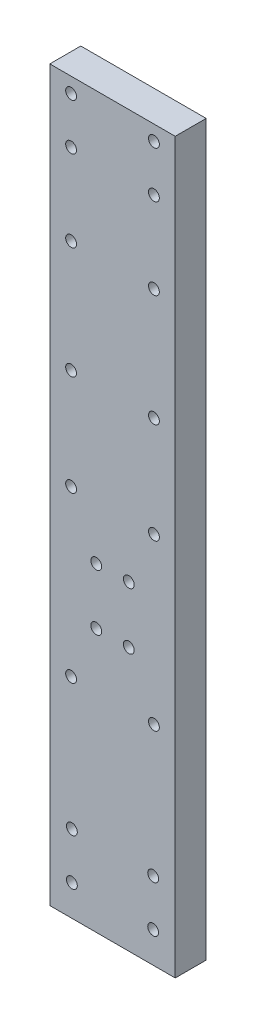
SolidWorks part; units mm, degrees
ref_plane "Front Plane" through (0, 0, 0) normal (0, 0, 1) x (1, 0, 0)
ref_plane "Top Plane" through (0, 0, 0) normal (0, 1, 0) x (1, 0, 0)
ref_plane "Right Plane" through (0, 0, 0) normal (1, 0, 0) x (0, 0, -1)
sketch "Sketch3" plane through (0, 0, 0) normal (0, 0, 1) x (1, 0, 0)
  line L0 (0, 94.0064) -> (0, -0.1536)
  line L1 (16.2, 94.0064) -> (16.2, -0.1536)
  line L2 (0, -0.1536) -> (16.2, -0.1536)
  line L4 (0, 94.0064) -> (16.2, 94.0064)
  line L5 (0, 12.3464) -> (16.2, 12.3464) construction
  line L6 (0, 58.6064) -> (16.2, 58.6064) construction
  line L26 (0, 50.6064) -> (16.2, 50.6064) construction
  line L27 (0, 24.3464) -> (16.2, 24.3464) construction
  line L30 (0, 78.0614) -> (16.2, 78.0614) construction
  line L32 (0, 84.0614) -> (16.2, 84.0614) construction
  circle A0 centre (6, 33.8464) radius 0.7
  circle A1 centre (10.2, 33.8464) radius 0.7
  circle A2 centre (2.75, 86.0614) radius 0.7
  circle A3 centre (10.2, 41.1664) radius 0.7
  circle A4 centre (13.45, 48.1064) radius 0.7
  circle A5 centre (2.75, 92.0614) radius 0.7
  circle A6 centre (13.45, 86.0614) radius 0.7
  circle A7 centre (2.75, 61.1064) radius 0.7
  circle A16 centre (2.85, 9.8464) radius 0.7
  circle A17 centre (13.35, 9.8464) radius 0.7
  circle A18 centre (13.35, 3.8464) radius 0.7
  circle A19 centre (2.85, 3.8464) radius 0.7
  circle A20 centre (13.45, 61.1064) radius 0.7
  circle A21 centre (2.75, 75.5614) radius 0.7
  circle A22 centre (13.45, 26.8464) radius 0.7
  circle A23 centre (13.45, 75.5614) radius 0.7
  circle A24 centre (13.45, 92.0614) radius 0.7
  circle A25 centre (2.75, 26.8464) radius 0.7
  circle A26 centre (6, 41.1064) radius 0.7
  circle A27 centre (2.75, 48.1064) radius 0.7
  dimension "D45" = 1.4
  dimension "D1" = 2.5
  dimension "D2" = 9.5
  dimension "D3" = 2.5
  dimension "D4" = 9.5
  dimension "D5" = 6
  dimension "D6" = 2.75
  dimension "D7" = 2.75
  dimension "D8" = 6
  dimension "D9" = 2.5
  dimension "D10" = 2.5
  dimension "D11" = 9.5
  dimension "D12" = 9.44
  dimension "D13" = 2.75
  dimension "D14" = 6
  dimension "D15" = 2.75
  dimension "D16" = 6
  dimension "D17" = 12
  dimension "D19" = 4
  dimension "D21" = 6
  dimension "D22" = 4
  dimension "D23" = 2.85
  dimension "D24" = 2.85
  dimension "D25" = 26.26
  dimension "D26" = 16.2
  dimension "D27" = 8
  dimension "D28" = 2.5
  dimension "D29" = 2.5
  dimension "D30" = 2.75
  dimension "D31" = 2.75
  dimension "D34" = 2.5
  dimension "D35" = 2.5
  dimension "D36" = 2.75
  dimension "D37" = 2.75
  dimension "D38" = 19.455
  dimension "D39" = 6
  dimension "D40" = 2
  dimension "D41" = 2
  dimension "D42" = 2.75
  dimension "D43" = 2.75
  dimension "D46" = 2.75
  dimension "D47" = 2.75
  dimension "D48" = 9.945
  dimension "D32" = 6
  dimension "D33" = 6
  dimension "D18" = 2.5
  dimension "D44" = 2.5
  dimension "D20" = 6
extrude "Boss-Extrude3" add sketch "Sketch3" along normal blind 4
equation "\"D25@Sketch3\"= \"HL@parametersSketch@prostheticParameters.SLDPRT\" * 0.196 - 4 - 6'Index PIP length"
equation "\"D26@Sketch3\"= \"fingerWidth@parametersSketch@prostheticParameters.SLDPRT\"'Index Width"
equation "\"D38@Sketch3\"= \"HL@parametersSketch@prostheticParameters.SLDPRT\" * 0.143 - 3 - 4 'Index MIP Length"
equation "\"D48@Sketch3\"= \"HL@parametersSketch@prostheticParameters.SLDPRT\" * 0.097 - 3 - 5'Index DIP Length - Gap Fingertip"
equation "\"D45@Sketch3\"= 1 + \"tol1@parametersSketch@prostheticParameters.SLDPRT\""
